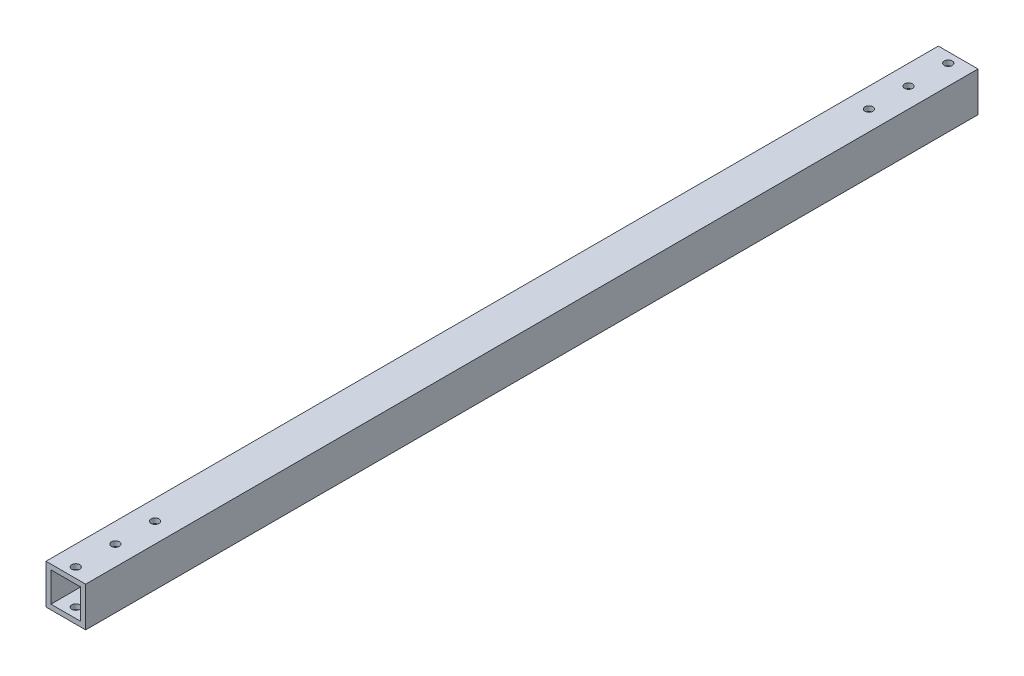
SolidWorks part; units mm, degrees
material "6061-T6 (SS)"
ref_plane "Front Plane" through (0, 0, 0) normal (0, 0, 1) x (1, 0, 0)
ref_plane "Top Plane" through (0, 0, 0) normal (0, 1, 0) x (1, 0, 0)
ref_plane "Right Plane" through (0, 0, 0) normal (1, 0, 0) x (0, 0, -1)
sketch "Sketch1" plane through (0, 0, 0) normal (0, 0, 1) x (1, 0, 0)
  line L1 (-12.7, -12.7) -> (12.7, -12.7)
  line L2 (-12.7, -12.7) -> (-12.7, 12.7)
  line L3 (-12.7, 12.7) -> (12.7, 12.7)
  line L4 (12.7, -12.7) -> (12.7, 12.7)
  line L5 (-12.7, -12.7) -> (12.7, 12.7) construction
  line L6 (-12.7, 12.7) -> (12.7, -12.7) construction
  point P0 (0, 0)
  dimension "D1" = 25.4
  dimension "D2" = 25.4
extrude "Extrude-Thin1" add sketch "Sketch1" along normal blind 571.5 thin thin type one direction reverse wall 3.175
hole_wizard "#10 Clearance Hole1" positions "3DSketch1" profile "Sketch3" hole size "#10" standard "ANSI Inch" end condition through all
sketch3d "3DSketch1"
  line L1 (12.7, 12.7, 0) -> (-12.7, 12.7, 0) construction
  line L6 (0, 12.7, 571.5) -> (0, 12.7, 0) construction
  line L7 (12.7, 12.7, 571.5) -> (-12.7, 12.7, 571.5) construction
  point P57 (0, 12.7, 6.35)
  point P59 (0, 12.7, 31.75)
  point P61 (0, 12.7, 57.15)
  point P63 (0, 12.7, 539.75)
  point P65 (0, 12.7, 514.35)
  point P67 (0, 12.7, 565.15)
  dimension "D1" = 25.4
  dimension "D2" = 25.4
  dimension "D3" = 6.35
  dimension "D4" = 25.4
  dimension "D5" = 25.4
  dimension "D6" = 6.35
sketch "Sketch3" plane through (0, 12.7, 565.15) normal (1, 0, 0) x (0, 0, 1)
  line L0 (0, 0) -> (0, 25.4)
  line L1 (0, 25.4) -> (2.5527, 25.4)
  line L2 (2.5527, 25.4) -> (2.5527, 0)
  line L5 (2.5527, 0) -> (0, 0)
  line L11 (0, -6.35) -> (0, 107.95) construction
  dimension "Thru Hole Dia." = 5.1054
  dimension "Thru Hole Depth" = 25.4
